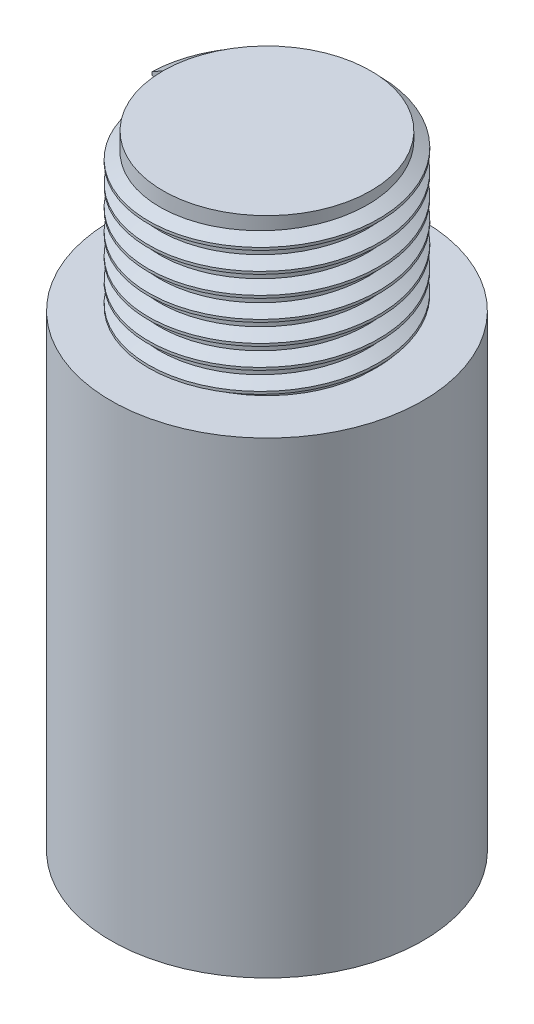
SolidWorks part; units mm, degrees
ref_plane "Front Plane" through (0, 0, 0) normal (0, 0, 1) x (1, 0, 0)
ref_plane "Top Plane" through (0, 0, 0) normal (0, 1, 0) x (1, 0, 0)
ref_plane "Right Plane" through (0, 0, 0) normal (1, 0, 0) x (0, 0, -1)
sketch "Sketch1" plane through (0, 0, 0) normal (0, 0, 1) x (1, 0, 0)
  line L0 (0, 0) -> (0, 38.1) construction
  line L1 (0, 0) -> (9.525, 0)
  line L2 (9.525, 0) -> (9.525, 28.575)
  line L3 (9.525, 28.575) -> (6.35, 28.575)
  line L4 (6.35, 28.575) -> (6.35, 38.1)
  line L5 (6.35, 38.1) -> (0, 38.1)
  line L6 (0, 0) -> (0, 38.1)
  point P3 (0, 51.534)
  dimension "D1" = 38.1
  dimension "D2" = 9.525
  dimension "D3" = 6.35
  dimension "D4" = 9.525
revolve "Revolve1" add sketch "Sketch1" angle 360 about L0
thread "Thread1" pitch 1.27 method extrude profile "Thread Profile2" start angle 0, offset 0, length 10, pitch 1.27, diameter 12.7
ref_plane "Plane2" through (-6.35, 38.1, 0) normal (0, 0, 1) x (-1, 0, 0)
sketch "Thread Profile2" plane through (-6.35, 38.1, 0) normal (0, 0, 1) x (-1, 0, 0)
  line L0 (0, 0) -> (0, 1.27) construction
  line L1 (0, 0) -> (0.6874, 0.3969)
  line L2 (0.6874, 0.3969) -> (0.6874, 0.5556)
  line L3 (0.6874, 0.5556) -> (0, 0.9525)
  line L4 (0.6874, 0.4762) -> (0, 0.4762) construction
  line L11 (0, 0) -> (0, 0.9525)
  point P2 (0, 0)
  dimension "Pitch" = 1.27
  dimension "Profile_Angle" = 60
  dimension "Profile_Land" = 0.1588
  dimension "Profile_Height" = 0.6874
